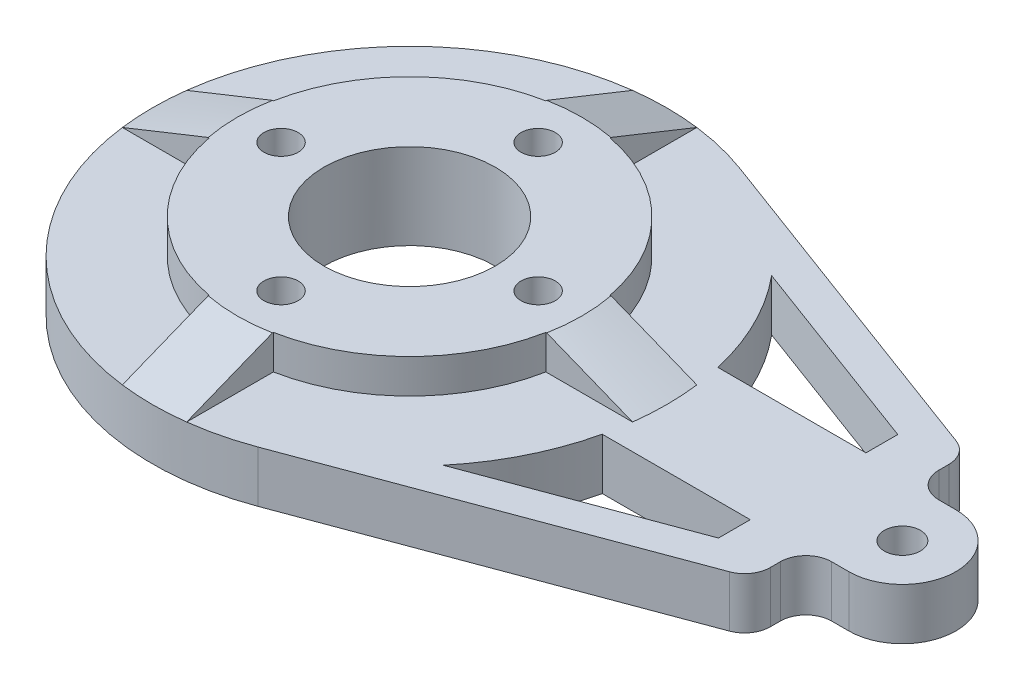
SolidWorks part; units mm, degrees
ref_plane "Front Plane" through (0, 0, 0) normal (0, 0, 1) x (1, 0, 0)
ref_plane "Top Plane" through (0, 0, 0) normal (0, 1, 0) x (1, 0, 0)
ref_plane "Right Plane" through (0, 0, 0) normal (1, 0, 0) x (0, 0, -1)
sketch "Sketch1" plane through (0, 0, 0) normal (0, 1, 0) x (1, 0, 0)
  circle A0 centre (0, 0) radius 20
  circle A1 centre (0, 0) radius 40
  dimension "D1" = 40
  dimension "D2" = 80
extrude "Boss-Extrude1" add sketch "Sketch1" along normal blind 8
sketch "Sketch3" plane through (0, 0, 0) normal (0, -1, 0) x (1, 0, 0)
  line L0 (20.8942, 56.2444) -> (105, 25)
  line L1 (105, 25) -> (105, -25)
  line L2 (105, -25) -> (20.8942, -56.2444)
  arc A0 (20.8942, 56.2444) -> (20.8942, -56.2444) centre (0, 0) ccw
  circle A2 centre (0, 0) radius 20
  circle A3 centre (0, 0) radius 20 construction
  point P6 (105, 0)
  dimension "D3" = 60
  dimension "D1" = 50
  dimension "D2" = 105
extrude "Boss-Extrude2" add sketch "Sketch3" along normal blind 12
sketch "Sketch5" plane through (0, -12, 0) normal (0, -1, 0) x (1, 0, 0)
  circle A0 centre (0, 30) radius 7.5
  circle A1 centre (30, 0) radius 7.5
  circle A2 centre (0, -30) radius 7.5
  circle A3 centre (-30, 0) radius 7.5
  point P12 (0, 0)
  dimension "D1" = 15
  dimension "D2" = 30
  dimension "D3" = 4
extrude "Cut-Extrude3" cut sketch "Sketch5" against normal blind 10
sketch "Sketch2" plane through (0, 8, 0) normal (0, 1, 0) x (1, 0, 0)
  circle A0 centre (30, 0) radius 4
  circle A1 centre (0, -30) radius 4
  circle A2 centre (-30, 0) radius 4
  circle A3 centre (0, 30) radius 4
  point P12 (0, 0)
  dimension "D1" = 8
  dimension "D2" = 30
  dimension "D3" = 4
extrude "Cut-Extrude1" cut sketch "Sketch2" against normal up to surface (20 mm away) up to face at (0, -12, 22.5)
sketch "Sketch6" plane through (0, 0, 0) normal (0, 1, 0) x (1, 0, 0)
  line L0 (-7.5, -39.2906) -> (-7.5, -59.5294)
  line L1 (7.5, -39.2906) -> (7.5, -59.5294)
  line L2 (-39.2906, -7.5) -> (-59.5294, -7.5)
  line L3 (-39.2906, 7.5) -> (-59.5294, 7.5)
  line L4 (-7.5, 39.2906) -> (-7.5, 59.5294)
  line L5 (7.5, 39.2906) -> (7.5, 59.5294)
  line L6 (39.2906, 7.5) -> (59.5294, 7.5)
  line L7 (39.2906, -7.5) -> (59.5294, -7.5)
  arc A0 (-7.5, -39.2906) -> (7.5, -39.2906) centre (0, 0) ccw
  circle A1 centre (0, 0) radius 40 construction
  arc A2 (-7.5, -59.5294) -> (7.5, -59.5294) centre (0, 0) ccw
  arc A3 (20.8942, 56.2444) -> (20.8942, -56.2444) centre (0, 0) ccw construction
  arc A4 (-59.5294, 7.5) -> (-59.5294, -7.5) centre (0, 0) ccw
  arc A5 (-39.2906, 7.5) -> (-39.2906, -7.5) centre (0, 0) ccw
  arc A6 (7.5, 59.5294) -> (-7.5, 59.5294) centre (0, 0) ccw
  arc A7 (7.5, 39.2906) -> (-7.5, 39.2906) centre (0, 0) ccw
  arc A8 (59.5294, -7.5) -> (59.5294, 7.5) centre (0, 0) ccw
  arc A9 (39.2906, -7.5) -> (39.2906, 7.5) centre (0, 0) ccw
  point P11 (0, -60)
  point P12 (0, -40)
  point P28 (0, 0)
  dimension "D1" = 15
  dimension "D2" = 4
extrude "Boss-Extrude3" add sketch "Sketch6" along normal up to surface (8 mm away) up to face at (30, 8, 4)
chamfer "Chamfer1" distance 8 angle 68 4 edges at (0, 8, -60) (60, 8, 0) (0, 8, 60) (-60, 8, 0) first distance on face at (-15.8462, 1.5, 0) first distance on face at (59.7647, 4, 0)
sketch "Sketch7" plane through (0, -12, 0) normal (0, -1, 0) x (1, 0, 0)
  line L2 (115, 12.5) -> (105, 12.5)
  line L3 (105, -25) -> (105, 25) construction
  line L4 (105, 12.5) -> (105, -12.5)
  line L5 (105, -12.5) -> (115, -12.5)
  arc A0 (115, 12.5) -> (115, -12.5) centre (115, 0) cw
  point P3 (105, 0)
  point P5 (105, 0)
  dimension "D1" = 25
  dimension "D2" = 10
extrude "Boss-Extrude4" add sketch "Sketch7" against normal up to surface (12 mm away) up to face at (40.8222, 0, 0)
fillet "Fillet1" radius 6 4 edges at (105, -6, 25) (105, -6, -25) (105, -6, -12.5) (105, -6, 12.5)
sketch "Sketch8" plane through (0, -12, 0) normal (0, -1, 0) x (1, 0, 0)
  line L1 (111.2472, -6.5) -> (118.7528, -6.5)
  line L2 (118.7528, -6.5) -> (122.5056, 0)
  line L3 (122.5056, 0) -> (118.7528, 6.5)
  line L4 (118.7528, 6.5) -> (111.2472, 6.5)
  line L5 (111.2472, 6.5) -> (107.4944, 0)
  line L6 (107.4944, 0) -> (111.2472, -6.5)
  circle A0 centre (115, 0) radius 6.5 construction
  arc A1 (115, -12.5) -> (115, 12.5) centre (115, 0) ccw construction
  point P13 (127.5, 0)
  dimension "D1" = 13
extrude "Cut-Extrude4" cut sketch "Sketch8" against normal blind 6
sketch "Sketch9" plane through (0, -6, 0) normal (0, -1, 0) x (1, 0, 0)
  circle A0 centre (115, 0) radius 4.2
  dimension "D1" = 8.4
extrude "Cut-Extrude5" cut sketch "Sketch9" against normal up to surface (6 mm away) up to face at (-31.9052, 0, -31.9052)
sketch "Sketch11" plane through (0, 0, 0) normal (0, 1, 0) x (1, 0, 0)
  line L1 (93, 20.9237) -> (93, 13.5)
  line L2 (93, 13.5) -> (58.4615, 13.5)
  line L5 (46.1679, 38.3213) -> (93, 20.9237)
  line L6 (20.8942, 56.2444) -> (101.0894, 26.4527) construction
  line L8 (59.5294, 7.5) -> (39.2906, 7.5) construction
  line L9 (105, 20.8283) -> (105, 18.5) construction
  arc A0 (58.4615, 13.5) -> (46.1679, 38.3213) centre (0, 0) ccw
  dimension "D1" = 60
  dimension "D2" = 8
  dimension "D4" = 6
  dimension "D5" = 12
extrude "Cut-Extrude7" cut sketch "Sketch11" against normal up to surface (12 mm away) up to face at (115, -12, 0)
mirror "Mirror1" about plane through (0, 0, 0) normal (0, 0, 1) of "Cut-Extrude7"
